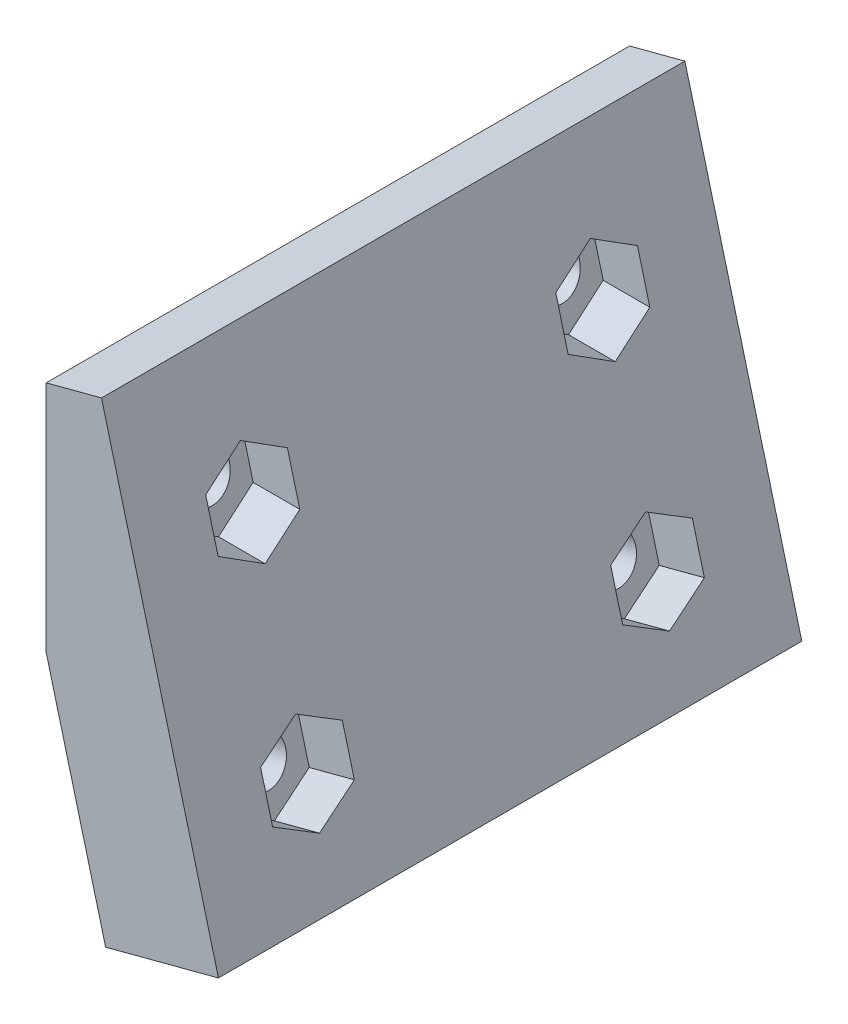
SolidWorks part; units mm, degrees
material "ABS"
ref_plane "Front Plane" through (0, 0, 0) normal (0, 0, 1) x (1, 0, 0)
ref_plane "Top Plane" through (0, 0, 0) normal (0, 1, 0) x (1, 0, 0)
ref_plane "Right Plane" through (0, 0, 0) normal (1, 0, 0) x (0, 0, -1)
sketch "Sketch1" plane through (0, 0, 0) normal (0, 0, 1) x (1, 0, 0)
  line L0 (0, -108) -> (0, -128)
  line L1 (0, -125.5) -> (0, 24.5) construction
  line L2 (0, -128) -> (5.0955, -147.34)
  line L3 (0, -125.5) -> (21.7, -218.5082) construction
  line L4 (5.0955, -147.34) -> (14.7655, -144.7922)
  line L5 (14.7655, -144.7922) -> (4.7426, -106.7505)
  line L6 (4.7426, -106.7505) -> (0, -108)
  point P5 (0, -128)
  dimension "D1" = 20
  dimension "D2" = 20
  dimension "D3" = 10
extrude "Boss-Extrude1" add sketch "Sketch1" against normal blind 50
sketch "Sketch2" plane through (0, 0, 0) normal (-1, 0, 0) x (0, 0, 1)
  line L0 (-50, -118) -> (0, -118) construction
  line L1 (-50, -108) -> (0, -108)
  line L2 (-50, -108) -> (-50, -128)
  line L3 (-50, -128) -> (0, -128)
  line L4 (0, -108) -> (0, -128)
  line L5 (-50, -108) -> (0, -128) construction
  line L6 (-50, -128) -> (0, -108) construction
  line L7 (-25, -108) -> (-25, -128) construction
  line L8 (-40, -113.9585) -> (-43.5, -115.9793)
  line L9 (-43.5, -115.9793) -> (-43.5, -120.0207)
  line L10 (-43.5, -120.0207) -> (-40, -122.0415)
  line L11 (-40, -122.0415) -> (-36.5, -120.0207)
  line L12 (-36.5, -120.0207) -> (-36.5, -115.9793)
  line L13 (-36.5, -115.9793) -> (-40, -113.9585)
  line L20 (-13.5, -115.9793) -> (-10, -113.9585)
  line L21 (-13.5, -120.0207) -> (-13.5, -115.9793)
  line L22 (-10, -122.0415) -> (-13.5, -120.0207)
  line L23 (-6.5, -120.0207) -> (-10, -122.0415)
  line L24 (-6.5, -115.9793) -> (-6.5, -120.0207)
  line L25 (-10, -113.9585) -> (-6.5, -115.9793)
  circle A0 centre (-40, -118) radius 3.5 construction
  circle A1 centre (-40, -118) radius 2
  circle A2 centre (-10, -118) radius 3.5 construction
  circle A3 centre (-10, -118) radius 2
  point P4 (-25, -118)
  dimension "D1" = 4
  dimension "D2" = 7
  dimension "D3" = 15
extrude "Cut-Extrude1" cut sketch "Sketch2" against normal blind 50 contours A1 | A3 region at (0, -118, -40) region at (0, -118, -10)
extrude "Cut-Extrude2" cut sketch "Sketch2<3>" along normal blind 4 from surface contours L12 L13 L8 L9 L10 L11 A1 | L25 L20 L21 L22 L23 L24 A3 region at (0, -115.0615, -38.3035) region at (0, -115.0615, -11.6965) starting at face at (7.1796, -116, -10)
sketch "Sketch2<3>" plane through (0, 0, 0) normal (-1, 0, 0) x (0, 0, 1) same geometry as "Sketch2"
sketch "Sketch3" plane through (-31.5353, -8.3087, 0) normal (-0.967, -0.2548, 0) x (0, 0, 1)
  line L1 (-50, -123.776) -> (0, -123.776)
  line L2 (-50, -123.776) -> (-50, -143.776)
  line L3 (-50, -143.776) -> (0, -143.776)
  line L4 (0, -123.776) -> (0, -143.776)
  line L5 (-50, -123.776) -> (0, -143.776) construction
  line L6 (-50, -143.776) -> (0, -123.776) construction
  line L7 (-25, -123.776) -> (-25, -143.776) construction
  line L8 (-40, -130.4399) -> (-43.5, -132.4607)
  line L9 (-43.5, -132.4607) -> (-43.5, -136.5021)
  line L10 (-43.5, -136.5021) -> (-40, -138.5229)
  line L11 (-40, -138.5229) -> (-36.5, -136.5021)
  line L12 (-36.5, -136.5021) -> (-36.5, -132.4607)
  line L13 (-36.5, -132.4607) -> (-40, -130.4399)
  line L14 (-13.5, -132.4607) -> (-10, -130.4399)
  line L15 (-13.5, -136.5021) -> (-13.5, -132.4607)
  line L16 (-10, -138.5229) -> (-13.5, -136.5021)
  line L17 (-6.5, -136.5021) -> (-10, -138.5229)
  line L18 (-6.5, -132.4607) -> (-6.5, -136.5021)
  line L19 (-10, -130.4399) -> (-6.5, -132.4607)
  circle A0 centre (-40, -134.4814) radius 2
  circle A1 centre (-40, -134.4814) radius 3.5 construction
  circle A2 centre (-10, -134.4814) radius 3.5 construction
  circle A3 centre (-10, -134.4814) radius 2
  ellipse E1 centre (-40, -134.4814) end of major axis (-42, -134.4814) minor radius 1.9997 construction
  point P4 (-25, -133.776)
  point P7 (-40, -134.3169)
  dimension "D3" = 4
  dimension "D2" = 7
extrude "Cut-Extrude3" cut sketch "Sketch3" against normal through all contours A0 | A3 region at (2.7275, -138.3522, -40) region at (2.7275, -138.3522, -10)
extrude "Cut-Extrude4" cut sketch "Sketch3<3>" along normal blind 4 from surface contours L12 L13 L8 L9 L10 L11 A0 | L19 L14 L15 L16 L17 L18 A3 region at (1.9788, -135.5106, -38.3035) region at (1.9788, -135.5106, -11.6965) starting at face at (11.8879, -133.8704, -10)
sketch "Sketch3<3>" plane through (-31.5353, -8.3087, 0) normal (-0.967, -0.2548, 0) x (0, 0, 1) same geometry as "Sketch3"
